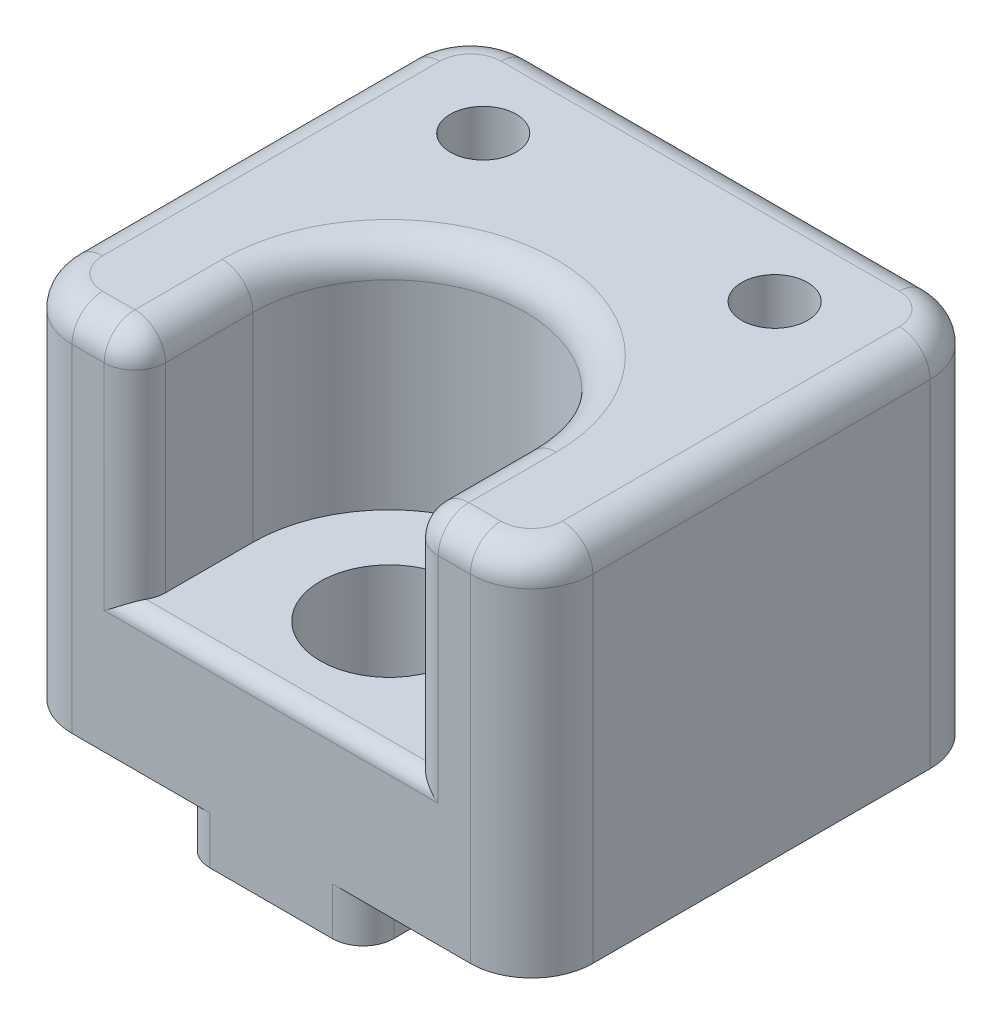
SolidWorks part; units mm, degrees
ref_plane "Front Plane" through (0, 0, 0) normal (0, 0, 1) x (1, 0, 0)
ref_plane "Top Plane" through (0, 0, 0) normal (0, 1, 0) x (1, 0, 0)
ref_plane "Right Plane" through (0, 0, 0) normal (1, 0, 0) x (0, 0, -1)
ref_plane "Plane1" through (0, -1.55, 0) normal (0, -1, 0) x (1, 0, 0)
sketch "Sketch1" plane through (0, -1.55, 0) normal (0, -1, 0) x (1, 0, 0)
  line L0 (8.5, 7.5) -> (-8.5, 7.5)
  line L1 (-8.5, 7.5) -> (-8.5, -7.5)
  line L2 (-8.5, -7.5) -> (8.5, -7.5)
  line L3 (8.5, -7.5) -> (8.5, 7.5)
extrude "Boss-Extrude1" add sketch "Sketch1" against normal blind 13.55
sketch "Sketch2" plane through (0, 0, -7.5) normal (0, 0, -1) x (-1, 0, 0)
  line L0 (-3, -1.55) -> (-3, 0)
  line L1 (-3, 0) -> (-8.5, 0)
  line L2 (-8.5, 0) -> (-8.5, -1.55)
  line L3 (-8.5, -1.55) -> (-3, -1.55)
extrude "Cut-Extrude1" cut sketch "Sketch2" against normal through all
sketch "Sketch3" plane through (0, 0, -7.5) normal (0, 0, -1) x (-1, 0, 0)
  line L0 (8.5, -1.55) -> (8.5, 0)
  line L1 (8.5, 0) -> (3, 0)
  line L2 (3, 0) -> (3, -1.55)
  line L3 (3, -1.55) -> (8.5, -1.55)
extrude "Cut-Extrude2" cut sketch "Sketch3" against normal through all
sketch "Sketch4" plane through (0, 12, 0) normal (0, 1, 0) x (-1, 0, 0)
  line L0 (-4.45, 7.5) -> (-4.45, 3.65)
  line L1 (4.45, 3.65) -> (4.45, 7.5)
  line L2 (4.45, 7.5) -> (-4.45, 7.5)
  arc A0 (-4.45, 3.65) -> (4.45, 3.65) centre (0, 3.65) ccw
extrude "Cut-Extrude3" cut sketch "Sketch4" against normal blind 7.5
sketch "Sketch5" plane through (0, -1.55, 0) normal (0, -1, 0) x (1, 0, 0)
  line L0 (-2.35, 7) -> (2.5, 7)
  line L1 (2.5, 7) -> (2.5, -7)
  line L2 (2.5, -7) -> (-2.35, -7)
  line L3 (-2.35, -7) -> (-2.35, 7)
extrude "Boss-Extrude2" add sketch "Sketch5" along normal blind 0.2
hole_wizard "Ø4.5 (4.5) Diameter Hole1" positions "Sketch7" profile "Sketch6" hole size "Ø4.5" standard "ANSI Metric"
sketch "Sketch7" plane through (0, 4.5, 0) normal (0, 1, 0) x (1, 0, 0)
  point P0 (0, -3.65)
sketch "Sketch6" plane through (0, 4.5, 3.65) normal (1, 0, 0) x (0, 0, 1)
  line L0 (0, 0) -> (0, 6.25)
  line L1 (0, 6.25) -> (2.25, 6.25)
  line L2 (2.25, 6.25) -> (2.25, 0)
  line L5 (2.25, 0) -> (0, 0)
  line L11 (0, -6.35) -> (0, 107.95) construction
  dimension "Thru Hole Dia." = 4.5
  dimension "Thru Hole Depth" = 6.25
hole_wizard "Ø2.15 (2.15) Diameter Hole1" positions "Sketch9" profile "Sketch8" hole size "Ø2.15" standard "ANSI Metric"
sketch "Sketch9" plane through (0, 12, 0) normal (0, 1, 0) x (1, 0, 0)
  point P0 (-4.755, 4.175)
  point P1 (4.755, 4.175)
sketch "Sketch8" plane through (-4.755, 12, -4.175) normal (1, 0, 0) x (0, 0, 1)
  line L0 (0, 0) -> (0, 10)
  line L1 (0, 10) -> (1.075, 10)
  line L2 (1.075, 10) -> (1.075, 0)
  line L5 (1.075, 0) -> (0, 0)
  line L10 (0, 10) -> (-1.075, 10) construction
  line L11 (0, -6.35) -> (0, 107.95) construction
  dimension "Hole Dia." = 2.15
  dimension "Hole Depth" = 10
  dimension "Drill Angle" = 180
fillet "Fillet1" radius 2 4 edges at (-8.5, 6, -7.5) (8.5, 6, -7.5) (8.5, 6, 7.5) (-8.5, 6, 7.5) tangent propagation no
fillet "Fillet2" radius 0.5 5 edges at (0, 4.5, 7.5) (2.5, -1.65, -7) (-2.35, -1.65, 7) (2.5, -1.65, 7) (-2.35, -1.65, -7) tangent propagation no
fillet "Fillet3" radius 1 18 edges at (4.45, 8, 7.5) (-4.45, 8, 7.5) (-5.475, 12, 7.5) (5.475, 12, 7.5) (-7.9142, 12, 6.9142) (7.9142, 12, 6.9142) (-8.5, 12, 0) (8.5, 12, 0) (-7.9142, 12, -6.9142) (7.9142, 12, -6.9142) (0, 12, -7.5) (-4.45, 12, 5.575) (0, 12, -0.8) (4.45, 12, 5.575) (3, -0.775, 7.5) (3, -0.775, -7.5) (-3, -0.775, 7.5) (-3, -0.775, -7.5) tangent propagation no
